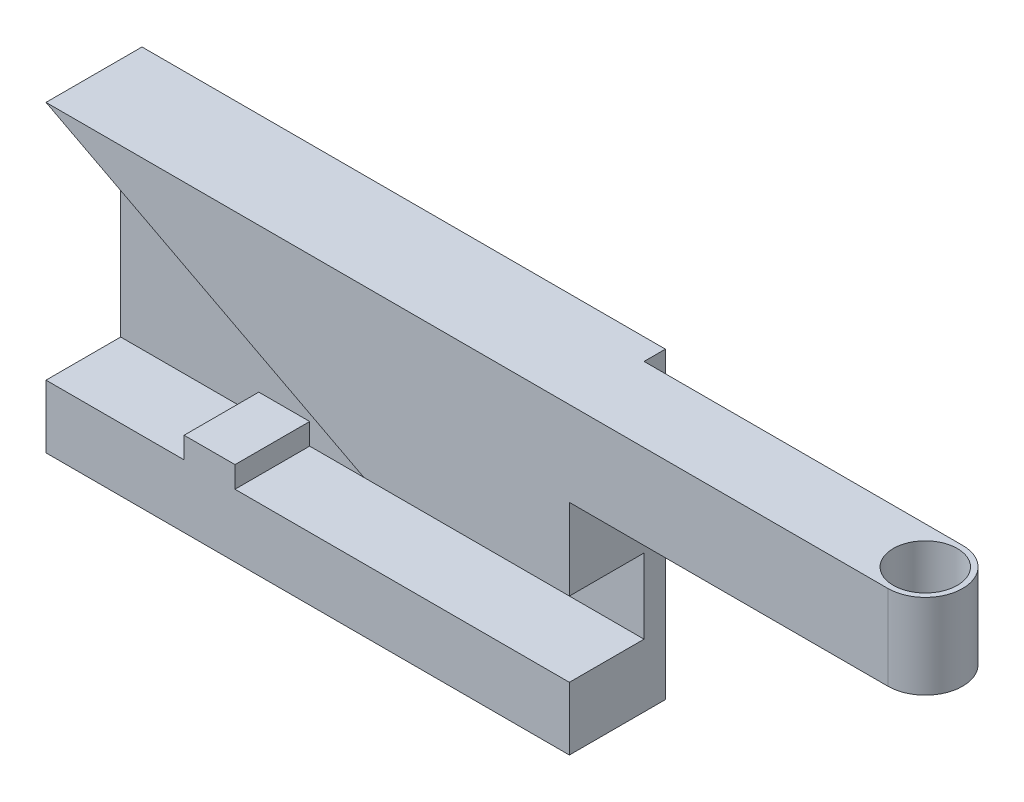
SolidWorks part; units mm, degrees
ref_plane "Front Plane" through (0, 0, 0) normal (0, 0, 1) x (1, 0, 0)
ref_plane "Top Plane" through (0, 0, 0) normal (0, 1, 0) x (1, 0, 0)
ref_plane "Right Plane" through (0, 0, 0) normal (1, 0, 0) x (0, 0, -1)
sketch "Sketch1" plane through (0, 0, 0) normal (0, 0, 1) x (1, 0, 0)
  line L0 (0, 0) -> (64.7345, 0)
  line L1 (245.3097, 35) -> (148.9823, 35)
  line L2 (148.9823, 35) -> (0, 112.7434)
  line L3 (88.5841, 0) -> (245.3097, 0)
  line L5 (64.7345, 0) -> (64.7345, 10)
  line L6 (64.7345, 10) -> (88.5841, 10)
  line L7 (88.5841, 0) -> (88.5841, 10)
  line L9 (245.3097, 73.0473) -> (245.3097, 35)
  line L10 (0, 0) -> (0, -29.5338)
  line L11 (0, -29.5338) -> (245.3097, -29.5338)
  line L12 (245.3097, -29.5338) -> (245.3097, 0)
  line L14 (0, 112.7434) -> (394.6315, 112.7434)
  line L16 (245.3097, 73.0473) -> (394.6315, 73.0473)
  line L17 (394.6315, 112.7434) -> (394.6315, 73.0473)
  point P16 (0, 0)
  point P17 (4.0313, 112.7434)
  dimension "D1" = 35
  dimension "D2" = 10
extrude "Boss-Extrude1" add sketch "Sketch1" along normal blind 35
sketch "Sketch2" plane through (0, 0, 0) normal (0, 0, -1) x (-1, 0, 0)
  line L1 (0, 112.7434) -> (-245.3097, 112.7434)
  line L2 (0, 112.7434) -> (0, -29.5338)
  line L3 (0, -29.5338) -> (-245.3097, -29.5338)
  line L4 (-245.3097, 112.7434) -> (-245.3097, -29.5338)
extrude "Boss-Extrude2" add sketch "Sketch2" along normal blind 10
sketch "Sketch3" plane through (0, 112.7434, 0) normal (0, 1, 0) x (1, 0, 0)
  circle A0 centre (394.6315, -17.5) radius 17.5
  circle A1 centre (394.6315, -17.5) radius 15
  dimension "D1" = 30
  dimension "D2" = 35
extrude "Boss-Extrude3" add sketch "Sketch3" against normal up to surface (39.696 mm away) up to face at (319.9706, 73.0473, 17.5)
sketch "Sketch4" plane through (0, 112.7434, 0) normal (0, 1, 0) x (1, 0, 0)
  circle A1 centre (394.6315, -17.5) radius 15
  circle A2 centre (394.6315, -17.5) radius 15
  dimension "D1" = 0
extrude "Cut-Extrude2" cut sketch "Sketch4" against normal up to next
